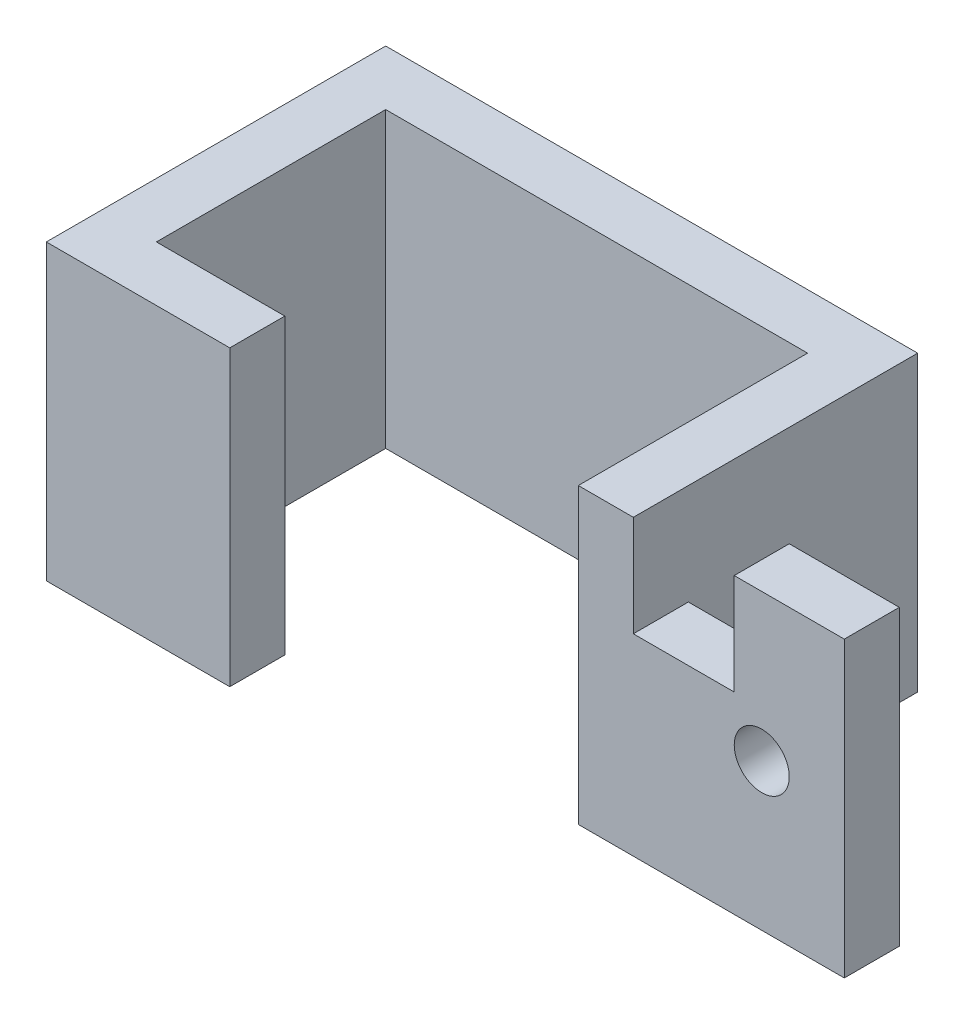
SolidWorks part; units mm, degrees
ref_plane "Front Plane" through (0, 0, 0) normal (0, 0, 1) x (1, 0, 0)
ref_plane "Top Plane" through (0, 0, 0) normal (0, 1, 0) x (1, 0, 0)
ref_plane "Right Plane" through (0, 0, 0) normal (1, 0, 0) x (0, 0, -1)
sketch "Sketch1" plane through (0, 0, 0) normal (0, 1, 0) x (1, 0, 0)
  line L1 (-14.5, 7.75) -> (14.5, 7.75)
  line L2 (-14.5, 7.75) -> (-14.5, -7.75)
  line L3 (-14.5, -7.75) -> (14.5, -7.75)
  line L4 (14.5, 7.75) -> (14.5, -7.75)
  line L5 (-14.5, 7.75) -> (14.5, -7.75) construction
  line L6 (-14.5, -7.75) -> (14.5, 7.75) construction
  point P0 (0, 0)
  dimension "D1" = 29
  dimension "D2" = 15.5
extrude "Boss-Extrude2" add sketch "Sketch1" along normal blind 16
sketch "Sketch2" plane through (0, 16, 0) normal (0, 1, 0) x (1, 0, 0)
  line L0 (-14.5, -7.75) -> (14.5, -7.75) construction
  line L1 (-11.5, 4.75) -> (11.5, 4.75)
  line L2 (-11.5, 4.75) -> (-11.5, -7.75)
  line L3 (-11.5, -7.75) -> (11.5, -7.75)
  line L4 (11.5, 4.75) -> (11.5, -7.75)
  line L5 (-11.5, 4.75) -> (11.5, -7.75) construction
  line L6 (-11.5, -7.75) -> (11.5, 4.75) construction
  point P0 (0, -1.5)
  dimension "D1" = 23
  dimension "D2" = 12.5
extrude "Cut-Extrude1" cut sketch "Sketch2" against normal up to next
sketch "Sketch3" plane through (14.5, 0, 0) normal (1, 0, 0) x (0, 0, -1)
  line L0 (-7.75, 16) -> (-7.75, 0) construction
  line L1 (-4.75, 16) -> (-7.75, 16)
  line L2 (-4.75, 16) -> (-4.75, 0)
  line L3 (-4.75, 0) -> (-7.75, 0)
  line L4 (-7.75, 16) -> (-7.75, 0)
  line L5 (-4.75, 16) -> (-7.75, 0) construction
  line L6 (-4.75, 0) -> (-7.75, 16) construction
  line L7 (-7.75, 0) -> (7.75, 0) construction
  line L8 (-7.75, 16) -> (7.75, 16) construction
  point P0 (-6.25, 8)
  dimension "D1" = 3
extrude "Boss-Extrude3" add sketch "Sketch3" along normal blind 13
sketch "Sketch4" plane through (-14.5, 0, 0) normal (-1, 0, 0) x (0, 0, 1)
  line L0 (7.75, 16) -> (7.75, 0) construction
  line L1 (4.75, 0) -> (7.75, 0)
  line L2 (4.75, 0) -> (4.75, 16)
  line L3 (4.75, 16) -> (7.75, 16)
  line L4 (7.75, 0) -> (7.75, 16)
  line L5 (4.75, 0) -> (7.75, 16) construction
  line L6 (4.75, 16) -> (7.75, 0) construction
  line L7 (-7.75, 0) -> (7.75, 0) construction
  line L8 (-7.75, 16) -> (7.75, 16) construction
  point P0 (6.25, 8)
  dimension "D1" = 3
extrude "Boss-Extrude4" add sketch "Sketch4" along normal blind 13
sketch "Sketch5" plane through (-14.5, 0, 0) normal (-1, 0, 0) x (0, 0, 1)
  line L0 (-7.75, 0) -> (4.75, 0) construction
  line L1 (-1.25, 0) -> (4.75, 0)
  line L2 (-1.25, 0) -> (-1.25, 5)
  line L3 (-1.25, 5) -> (4.75, 5)
  line L4 (4.75, 0) -> (4.75, 5)
  line L5 (-1.25, 0) -> (4.75, 5) construction
  line L6 (-1.25, 5) -> (4.75, 0) construction
  point P0 (1.75, 2.5)
  dimension "D1" = 6
  dimension "D2" = 6
  dimension "D3" = 5
extrude "Boss-Extrude6" add sketch "Sketch5" along normal blind 2
sketch "Sketch6" plane through (14.5, 0, 0) normal (1, 0, 0) x (0, 0, -1)
  line L0 (-4.75, 0) -> (7.75, 0) construction
  line L1 (1.25, 5) -> (-4.75, 5)
  line L2 (1.25, 5) -> (1.25, 0)
  line L3 (1.25, 0) -> (-4.75, 0)
  line L4 (-4.75, 5) -> (-4.75, 0)
  line L5 (1.25, 5) -> (-4.75, 0) construction
  line L6 (1.25, 0) -> (-4.75, 5) construction
  point P0 (-1.75, 2.5)
  dimension "D1" = 6
  dimension "D2" = 6
  dimension "D3" = 5
extrude "Boss-Extrude7" add sketch "Sketch6" along normal blind 2
sketch "Sketch7" plane through (0, 0, 0) normal (0, -1, 0) x (-1, 0, 0)
  line L0 (-11.5, -7.75) -> (-27.5, -7.75) construction
  circle A0 centre (14, -1.5) radius 1.5
  circle A1 centre (-14, -1.5) radius 1.5
  dimension "D2" = 3
  dimension "D3" = 3
  dimension "D1" = 28
  dimension "D4" = 14
  dimension "D5" = 6.25
extrude "Cut-Extrude2" cut sketch "Sketch7" against normal blind 5
sketch "Sketch8" plane through (0, 0, 4.75) normal (0, 0, -1) x (-1, 0, 0)
  line L0 (-27.5, 0) -> (-27.5, 16) construction
  line L1 (27.5, 16) -> (27.5, 0) construction
  circle A0 centre (-21.5, 8) radius 1.5
  circle A1 centre (21.5, 8) radius 1.5
  point P7 (-27.5, 8)
  dimension "D1" = 3
  dimension "D2" = 3
  dimension "D3" = 6
  dimension "D4" = 6
  dimension "D5" = 8
extrude "Cut-Extrude3" cut sketch "Sketch8" against normal up to next
sketch "Sketch9" plane through (0, 0, 4.75) normal (0, 0, -1) x (-1, 0, 0)
  line L1 (-26, 0) -> (-27.5, 0)
  line L2 (-26, 0) -> (-26, 16)
  line L3 (-26, 16) -> (-27.5, 16)
  line L4 (-27.5, 0) -> (-27.5, 16)
  line L5 (-26, 0) -> (-27.5, 16) construction
  line L6 (-26, 16) -> (-27.5, 0) construction
  point P0 (-26.75, 8)
  dimension "D1" = 1.5
extrude "Cut-Extrude4" cut sketch "Sketch9" against normal up to next
sketch "Sketch10" plane through (0, 0, 4.75) normal (0, 0, -1) x (-1, 0, 0)
  line L1 (27.5, 0) -> (14.5, 0)
  line L2 (27.5, 0) -> (27.5, 16)
  line L3 (27.5, 16) -> (14.5, 16)
  line L4 (14.5, 0) -> (14.5, 16)
  line L5 (27.5, 0) -> (14.5, 16) construction
  line L6 (27.5, 16) -> (14.5, 0) construction
  point P0 (21, 8)
  point P5 (0, 0)
  point P7 (0, 0)
  point P9 (0, 0)
extrude "Cut-Extrude5" cut sketch "Sketch10" against normal up to next
sketch "Sketch11" plane through (-14.5, 0, 0) normal (-1, 0, 0) x (0, 0, 1)
  line L1 (7.75, 16) -> (10.75, 16)
  line L2 (7.75, 16) -> (7.75, 0)
  line L3 (7.75, 0) -> (10.75, 0)
  line L4 (10.75, 16) -> (10.75, 0)
  line L5 (7.75, 16) -> (10.75, 0) construction
  line L6 (7.75, 0) -> (10.75, 16) construction
  point P0 (9.25, 8)
  point P5 (0, 0)
  point P7 (0, 0)
  dimension "D1" = 3
extrude "Boss-Extrude8" add sketch "Sketch11" against normal blind 10
sketch "Sketch12" plane through (0, 0, 4.75) normal (0, 0, -1) x (-1, 0, 0)
  line L0 (-14.5, 5) -> (-14.5, 16) construction
  line L1 (-14.5, 10.5) -> (-20, 10.5)
  line L2 (-14.5, 10.5) -> (-14.5, 16)
  line L3 (-14.5, 16) -> (-20, 16)
  line L4 (-20, 10.5) -> (-20, 16)
  line L5 (-14.5, 10.5) -> (-20, 16) construction
  line L6 (-14.5, 16) -> (-20, 10.5) construction
  line L7 (-26, 16) -> (-14.5, 16) construction
  point P0 (-17.25, 13.25)
  point P9 (-20.0942, 10.5946)
  dimension "D1" = 5.5
  dimension "D2" = 5.5
extrude "Cut-Extrude6" cut sketch "Sketch12" against normal up to next
fillet "Fillet1" radius 4 2 edges at (15.5, 5, 4.75) (16.5, 2.5, 4.75)
